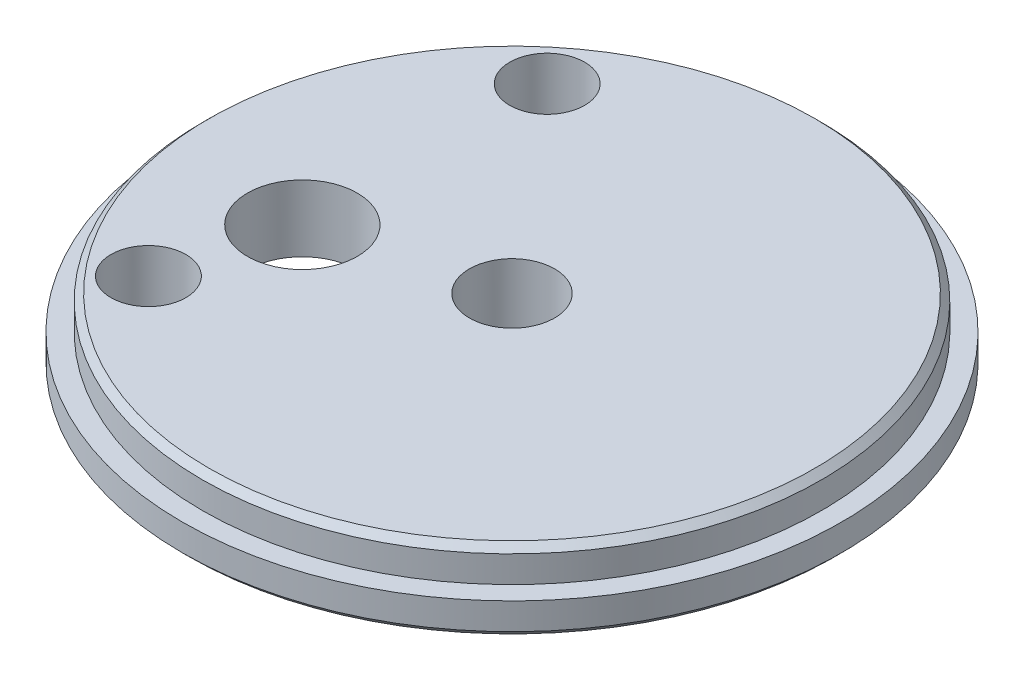
SolidWorks part; units mm, degrees
material "6061-T6 (SS)"
ref_plane "Front Plane" through (0, 0, 0) normal (0, 0, 1) x (1, 0, 0)
ref_plane "Top Plane" through (0, 0, 0) normal (0, 1, 0) x (1, 0, 0)
ref_plane "Right Plane" through (0, 0, 0) normal (1, 0, 0) x (0, 0, -1)
sketch "Sketch1" plane through (0, 0, 0) normal (0, 1, 0) x (1, 0, 0)
  circle A0 centre (0, 0) radius 25.146
  dimension "D1" = 50.292
extrude "Boss-Extrude1" add sketch "Sketch1" along normal blind 2.54
sketch "Sketch2" plane through (0, 2.54, 0) normal (0, 1, 0) x (1, 0, 0)
  circle A0 centre (0, 0) radius 23.622
  dimension "D1" = 47.244
extrude "Boss-Extrude2" add sketch "Sketch2" along normal blind 2.54
sketch "Sketch3" plane through (0, 0, 0) normal (0, -1, 0) x (1, 0, 0)
  circle A0 centre (0, 0) radius 3.2512
  circle A3 centre (-12.5377, 3.46) radius 4.191
  dimension "D1" = 6.5024
  dimension "D2" = 8.382
extrude "Cut-Extrude1" cut sketch "Sketch3" against normal through all and the other way through all
sketch "Sketch4" plane through (0, 0, 0) normal (0, -1, 0) x (1, 0, 0)
  circle A0 centre (-12.5126, -15.1965) radius 2.8575
  circle A1 centre (-15.019, 12.7251) radius 2.8575
  circle A2 centre (0, 0) radius 19.685 construction
  point P4 (-10.2595, -13.7281)
  point P5 (-13.7311, 12.3476)
  point P6 (-15.7369, 12.8876)
  point P7 (-12.5126, -15.1965)
  point P12 (0, 0)
  point P13 (-15.019, 12.7251)
  dimension "D1" = 5.715
extrude "Cut-Extrude2" cut sketch "Sketch4" against normal up to surface (5.08 mm away) up to face at (0, 5.08, -3.2512)
chamfer "Chamfer1" distance 0.508 angle 45 2 edges at (0, 0, 25.146) (0, 5.08, 23.622)
